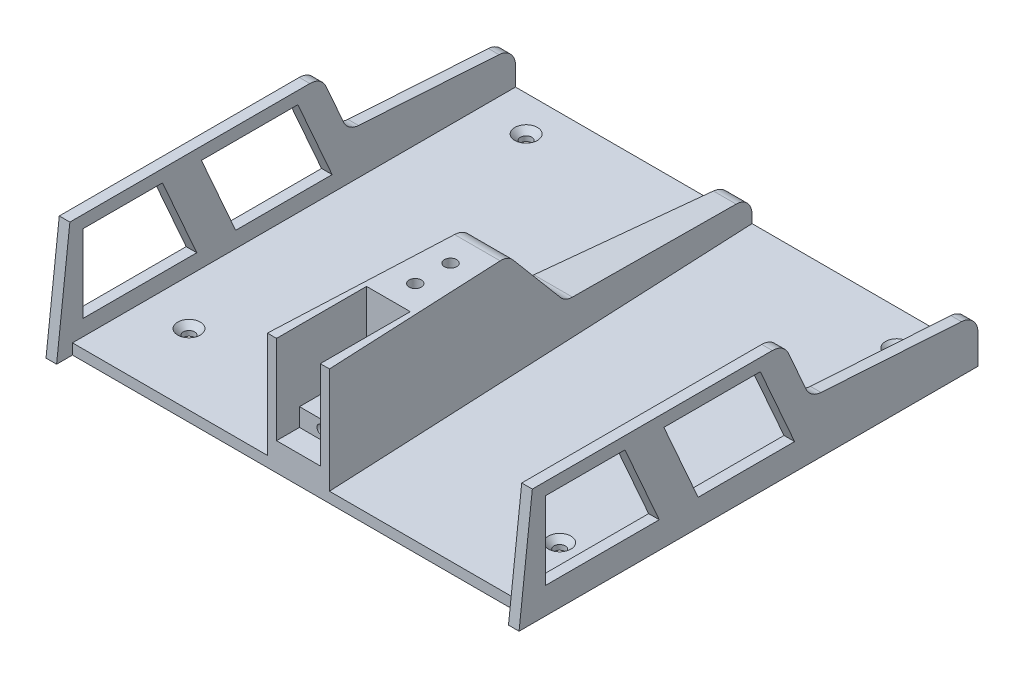
SolidWorks part; units mm, degrees
ref_plane "Front Plane" through (0, 0, 0) normal (0, 0, 1) x (1, 0, 0)
ref_plane "Top Plane" through (0, 0, 0) normal (0, 1, 0) x (1, 0, 0)
ref_plane "Right Plane" through (0, 0, 0) normal (1, 0, 0) x (0, 0, -1)
sketch "Sketch2" plane through (0, 0, 0) normal (0, 1, 0) x (1, 0, 0)
  line L0 (0, -652.4473) -> (0, 31969.9164) construction
  line L1 (-64, 130) -> (-64, 0)
  line L2 (67, 0) -> (-67, 0)
  line L3 (0, 0) -> (0, 130)
  line L4 (67, 130) -> (-67, 130)
  line L5 (-67, 0) -> (-67, 130)
  line L6 (-3, 130) -> (-9, 0)
  line L7 (3, 130) -> (9, 0)
  line L8 (67, 0) -> (67, 130)
  line L9 (64, 130) -> (64, 0)
  dimension "D1" = 3
  dimension "D2" = 3
  dimension "D3" = 9
  dimension "D4" = 55
  dimension "D5" = 130
extrude "Boss-Extrude1" add sketch "Sketch2" against normal blind 3 contours L6 L4 L1 L2 | L5 L2 L1 L4 | L4 L6 L2 L3 | L7 L4 L3 L2 | L9 L4 L7 L2 | L4 L9 L2 L8 region at (-34.9741, 0, -66.1207) region at (-65.5, 0, -65) region at (-3.25, 0, -54.1667) region at (3.25, 0, -54.1667) region at (34.9741, 0, -66.1207) region at (65.5, 0, -65)
extrude "Boss-Extrude2" add sketch "Sketch2<3>" along normal blind 30 contours L4 L6 L2 L3 | L7 L4 L3 L2 | L5 L2 L1 L4 | L4 L9 L2 L8 region at (-65.5, 0, -65) region at (-3.25, 0, -54.1667) region at (3.25, 0, -54.1667) region at (65.5, 0, -65)
sketch "Sketch2<3>" plane through (0, 0, 0) normal (0, 1, 0) x (1, 0, 0) same geometry as "Sketch2"
sketch "Sketch5" plane through (-67, 0, 0) normal (-1, 0, 0) x (0, 0, 1)
  line L0 (-130, 10) -> (-82.5, 13)
  line L1 (-130, -3) -> (-130, 30) construction
  line L2 (-82.5, 13) -> (-75, 30)
  line L3 (0, 30) -> (-130, 30) construction
  line L4 (0, -3) -> (-130, -3) construction
  line L5 (-82.5, 13) -> (-82.5, -3)
  line M3 (0, 30) -> (-130, 30)
  line M4 (-130, 30) -> (-130, -3)
  dimension "D1" = 13
  dimension "D2" = 16
  dimension "D3" = 47.5
  dimension "D4" = 55
extrude "Cut-Extrude2" cut sketch "Sketch5" against normal up to surface (3 mm away) contours L0 L2 M3 M4 region at (-67, 20.9735, -105.0729) up to face at (-64, 15, -65)
sketch "Sketch6" plane through (67, 0, 0) normal (1, 0, 0) x (0, 0, -1)
  line L0 (82.5, 13) -> (75, 30) construction
  line L1 (82.5, 13) -> (82.5, -3) construction
  line L2 (130, 10) -> (82.5, 13) construction
  line L3 (82.5, 13) -> (75, 30)
  line L4 (82.5, 13) -> (82.5, -3)
  line L5 (130, 10) -> (82.5, 13)
  line M1 (130, -3) -> (130, 30)
  line M2 (130, 30) -> (0, 30)
extrude "Cut-Extrude3" cut sketch "Sketch6" against normal blind 3 and the other way through all contours L5 L3 M1 M2 region at (67, 20.9735, -105.0729)
ref_plane "Plane1" through (1.5, 0, 0) normal (-1, 0, 0) x (0, 0, 1)
sketch "Sketch7" plane through (1.5, 0, -0.1871) normal (1, 0, 0) x (0, 0, -1)
  line L0 (129.8129, 30) -> (129.8129, 0) construction
  line L1 (129.8129, 30) -> (-0.1871, 30) construction
  line L2 (74.3129, 10) -> (129.8129, 10) construction
  line L3 (129.8129, 7) -> (74.3129, 10)
  line L4 (74.3129, 10) -> (57.3129, 30)
  line L5 (57.3129, 30) -> (129.8129, 30)
  line L6 (129.8129, 30) -> (129.8129, 7)
  point P0 (74.3129, 10)
  point P5 (129.8129, 10)
  point P8 (57.3129, 30)
  point P10 (129.8129, 7)
  dimension "D1" = 55.5
  dimension "D2" = 20
  dimension "D3" = 72.5
  dimension "D4" = 3
extrude "Cut-Extrude4" cut sketch "Sketch7" against normal up to surface and the other way up to surface up to face at (-6, 15, -65) other way up to face at (6, 15, -65)
sketch "Sketch9" plane through (0, 0, 0) normal (0, 0, 1) x (1, 0, 0)
  line L0 (67, -3) -> (-67, -3) construction
  line L1 (9, 30) -> (-9, 30) construction
  line L3 (9, 30) -> (9, 0) construction
  line L4 (-6.2, 30) -> (6.2, 30)
  line L5 (-6.2, 30) -> (-6.2, 10)
  line L6 (-6.2, 10) -> (6.2, 10)
  line L7 (6.2, 30) -> (6.2, 10)
  line L8 (-9, 30) -> (9, 30)
  line L9 (-9, 30) -> (-9, 0)
  line L10 (-9, 0) -> (9, 0)
  line L11 (9, 30) -> (9, 0)
  line L12 (64, 0) -> (9, 0) construction
  line L13 (0, 10) -> (0, 4.9) construction
  line L14 (-6.2, 10) -> (6.2, 10)
  line L15 (-6.2, 10) -> (-6.2, 4.9)
  line L16 (-6.2, 4.9) -> (6.2, 4.9)
  line L17 (6.2, 10) -> (6.2, 4.9)
  line L18 (-64, 0) -> (64, 0)
  line L19 (-64, 0) -> (-64, -3)
  line L20 (-64, -3) -> (64, -3)
  line L21 (64, 0) -> (64, -3)
  line L22 (64, 30) -> (64, 0) construction
  circle A0 centre (0, 7.45) radius 1.25
  point P10 (0, 30)
  point P22 (0, 7.45)
  line M15 (64, 0) -> (9, 0)
  line M16 (9, 0) -> (9, 30)
  line M17 (9, 30) -> (-9, 30)
  line M18 (-9, 30) -> (-9, 0)
  line M19 (-9, 0) -> (-64, 0)
  line M23 (-67, -3) -> (67, -3)
  dimension "D4" = 2.5
  dimension "D1" = 12.4
  dimension "D2" = 20
  dimension "D3" = 5.1
extrude "Cut-Extrude5" cut sketch "Sketch9" against normal blind 30 contours L7 L5 L6 L14 M17 region at (0, 20, 0)
extrude "Cut-Extrude6" cut sketch "Sketch9<3>" against normal blind 11 contours L13 L6 L15 L16 A0 | L14 L13 A0 L16 L17 region at (-3.3162, 7.45, 0) region at (3.3162, 7.45, 0)
sketch "Sketch9<3>" plane through (0, 0, 0) normal (0, 0, 1) x (1, 0, 0) same geometry as "Sketch9"
extrude "Cut-Extrude7" cut sketch "Sketch9<4>" against normal blind 4.5 contours L7 L17 L16 L15 L5 L10 M17 M18 M16 | L21 L10 L19 M15 M19 M23 region at (-6.5499, 20, 0) region at (0, -1.5, 0)
sketch "Sketch9<4>" plane through (0, 0, 0) normal (0, 0, 1) x (1, 0, 0) same geometry as "Sketch9"
extrude "Cut-Extrude8" cut sketch "Sketch9<5>" against normal blind 17 contours A0 L13 | L13 A0 region at (0.5305, 7.45, 0) region at (-0.5305, 7.45, 0)
sketch "Sketch9<5>" plane through (0, 0, 0) normal (0, 0, 1) x (1, 0, 0) same geometry as "Sketch9"
sketch "Sketch3" plane through (-67, 0, 0) normal (-1, 0, 0) x (0, 0, 1)
  line L0 (-82.5, 13) -> (-75, 30) construction
  line L2 (0, 30) -> (-75, 30) construction
  line L3 (-78.0525, 4.5) -> (-68.3467, 26.5)
  line L4 (-68.3467, 26.5) -> (-41.0218, 26.5)
  line L5 (-41.0218, 26.5) -> (-50.7277, 4.5)
  line L6 (-50.7277, 4.5) -> (-78.0525, 4.5)
  line L10 (-39.7059, 4.5) -> (-30, 4.5)
  line L11 (-30, 4.5) -> (-30, 26.5)
  line L15 (-30, 26.5) -> (-39.7059, 4.5)
  line L16 (-41.0218, 26.5) -> (-30, 26.5) construction
  line L17 (0, -3) -> (0, 30) construction
  line L18 (-30, 26.5) -> (-7.5, 26.5)
  line L19 (-30, 26.5) -> (-30, 4.5)
  line L20 (-30, 4.5) -> (-7.5, 4.5)
  line L21 (-7.5, 26.5) -> (-7.5, 4.5)
  dimension "D1" = 7.5
  dimension "D2" = 7.5
  dimension "D3" = 22
  dimension "D4" = 3.5
  dimension "D5" = 25
  dimension "D6" = 22.5
extrude "Cut-Extrude1" cut sketch "Sketch3" against normal up to surface (3 mm away) contours L6 L5 L4 L3 | L21 L18 L11 L20 | L11 L15 L10 region at (-67, 15.5, -59.5372) region at (-67, 11.8333, -33.2353) region at (-67, 15.5, -18.75) up to face at (-64, 9.625, -53.3125)
sketch "Sketch10" plane through (67, 0, 0) normal (1, 0, 0) x (0, 0, -1)
  line L0 (50.7277, 4.5) -> (78.0525, 4.5) construction
  line L1 (41.0218, 26.5) -> (50.7277, 4.5) construction
  line L2 (68.3467, 26.5) -> (41.0218, 26.5) construction
  line L3 (78.0525, 4.5) -> (68.3467, 26.5) construction
  line L4 (7.5, 26.5) -> (7.5, 4.5) construction
  line L5 (30, 26.5) -> (7.5, 26.5) construction
  line L6 (30, 26.5) -> (39.7059, 4.5) construction
  line L7 (39.7059, 4.5) -> (30, 4.5) construction
  line L8 (30, 4.5) -> (30, 26.5) construction
  line L9 (30, 4.5) -> (7.5, 4.5) construction
  line L10 (50.7277, 4.5) -> (78.0525, 4.5)
  line L11 (41.0218, 26.5) -> (50.7277, 4.5)
  line L12 (68.3467, 26.5) -> (41.0218, 26.5)
  line L13 (78.0525, 4.5) -> (68.3467, 26.5)
  line L14 (7.5, 26.5) -> (7.5, 4.5)
  line L15 (30, 26.5) -> (7.5, 26.5)
  line L16 (30, 26.5) -> (39.7059, 4.5)
  line L17 (39.7059, 4.5) -> (30, 4.5)
  line L18 (30, 4.5) -> (30, 26.5)
  line L19 (30, 4.5) -> (7.5, 4.5)
extrude "Cut-Extrude9" cut sketch "Sketch10" against normal up to surface (3 mm away) contours L19 L18 L15 L14 | L18 L17 L16 | L10 L13 L12 L11 region at (67, 15.5, -59.5372) region at (67, 15.5, -18.75) region at (67, 11.8333, -33.2353) up to face at (64, 9.625, -53.3125)
sketch "Sketch11" plane through (-67, 0, 0) normal (-1, 0, 0) x (0, 0, 1)
  line L0 (0, -3) -> (-3.7599, 30)
  line L1 (0, 30) -> (-75, 30) construction
  line L2 (-3.7599, 30) -> (0, 30)
  line L3 (0, 30) -> (0, -3)
  dimension "D1" = 83.5
extrude "Cut-Extrude10" cut sketch "Sketch11" against normal through all
fillet "Fillet1" radius 5 9 edges at (-65.5, 30, -75) (-65.5, 10, -130) (-65.5, 13, -82.5) (0, 30, -57.5) (0, 10, -74.5) (0, 7, -130) (65.5, 10, -130) (65.5, 30, -75) (65.5, 13, -82.5)
sketch "Sketch12" plane through (0, 30, 0) normal (0, 1, 0) x (1, 0, 0)
  line L0 (0, 30) -> (0, 55.1878) construction
  line L1 (6.2, 30) -> (-6.2, 30) construction
  line L2 (6.4529, 55.1878) -> (-6.4529, 55.1878) construction
  point P6 (0, 47.5939)
  point P7 (0, 37.5939)
  point P8 (0, 42.5939)
  dimension "D1" = 5
  dimension "D2" = 5
hole_wizard "Hole1" positions "3DSketch1" profile "Sketch13" legacy
sketch3d "3DSketch1"
  point P0 (0, 30, -47.5939)
  point P3 (0, 30, -37.5939)
sketch "Sketch13" plane through (0, 30, -47.5939) normal (1, 0, 0) x (0, 0, 1)
  line L0 (0, 0) -> (0, 20)
  line L1 (0, 20) -> (1.75, 20)
  line L2 (1.75, 20) -> (1.75, 0)
  line L3 (1.75, 0) -> (0, 0)
  line L4 (0, 110) -> (0, -10) construction
  dimension "Diameter" = 3.5
  dimension "Depth" = 20
sketch "Sketch14" plane through (0, 0, 0) normal (0, 1, 0) x (1, 0, 0)
  line L0 (64, 71.7409) -> (64, 3.7599) construction
  line L1 (64, 4.5) -> (8.7923, 4.5) construction
  line L2 (64, 125.3152) -> (64, 85.5328) construction
  line L3 (64, 130) -> (3, 130) construction
  line L4 (1.5, 16.5) -> (1.5, -16.5) construction
  point P0 (54, 24.5)
  point P5 (54, 120)
  point P12 (-51, 120)
  point P13 (-51, 24.5)
  dimension "D1" = 10
  dimension "D2" = 20
  dimension "D3" = 10
  dimension "D4" = 10
hole_wizard "Hole2" positions "3DSketch2" profile "Sketch15" legacy
sketch3d "3DSketch2"
  point P0 (-51, 0, -120)
  point P3 (54, 0, -120)
  point P6 (54, 0, -24.5)
  point P9 (-51, 0, -24.5)
sketch "Sketch15" plane through (-51, 0, -120) normal (1, 0, 0) x (0, 0, 1)
  line L0 (0, 0) -> (0, 4.7371)
  line L1 (0, 4.7371) -> (1.6, 4.7371)
  line L2 (1.6, 4.7371) -> (1.6, 1.6)
  line L3 (1.6, 1.6) -> (3.2, 0)
  line L4 (3.2, 0) -> (0, 0)
  line L5 (0, -6.4453) -> (0, 115.525) construction
  line L6 (-1.6, 1.6) -> (-3.2, 0) construction
  dimension "Diameter" = 3.2
  dimension "Depth" = 5
  dimension "C-Sink Angle" = 90
  dimension "C-Sink Diameter" = 6.4
